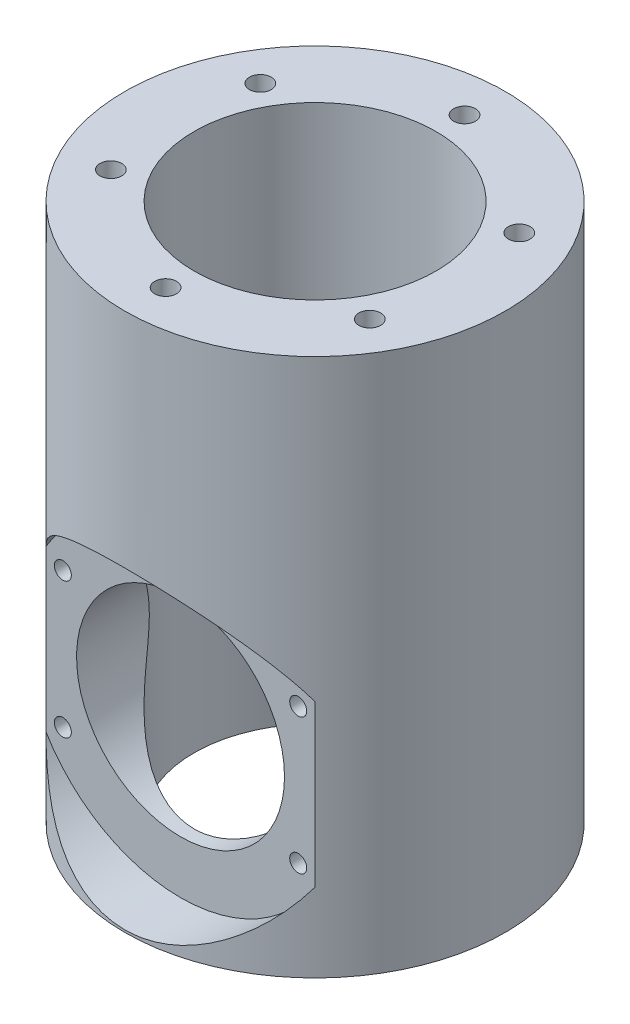
SolidWorks part; units mm, degrees
material "1060 Alloy"
ref_plane "Front Plane" through (0, 0, 0) normal (0, 0, 1) x (1, 0, 0)
ref_plane "Top Plane" through (0, 0, 0) normal (0, 1, 0) x (1, 0, 0)
ref_plane "Right Plane" through (0, 0, 0) normal (1, 0, 0) x (0, 0, -1)
sketch "Sketch1" plane through (0, 0, 0) normal (0, 0, 1) x (1, 0, 0)
  circle A0 centre (0, 0) radius 6.65
  circle A1 centre (0, 0) radius 7.15
  dimension "D1" = 13.3
  dimension "D2" = 14.3
extrude "Boss-Extrude1" add sketch "Sketch1" along normal blind 5
sketch "Sketch2" plane through (0, 0, 0) normal (0, 1, 0) x (1, 0, 0)
  circle A0 centre (0, 8.9) radius 8.9
  circle A1 centre (0, 8.9) radius 14
  dimension "D1" = 17.8
  dimension "D2" = 28
extrude "Boss-Extrude2" add sketch "Sketch2" along normal blind 27.9 and the other way blind 11.7
ref_plane "Plane4" through (0, -11.7, 0) normal (0, -1, 0) x (-1, 0, 0)
sketch "Sketch16" plane through (0, 0, 5) normal (0, 0, 1) x (1, 0, 0)
  circle A0 centre (0, 0) radius 6.65
  circle A1 centre (0, 0) radius 6.65 construction
  dimension "D1" = 0
extrude "Cut-Extrude3" cut sketch "Sketch16" against normal blind 17 and the other way blind 7
sketch "Sketch23" plane through (0, 0, 5) normal (0, 0, 1) x (1, 0, 0)
  circle A0 centre (0, 0) radius 7.05
  circle A1 centre (0, 0) radius 6.65
  circle A2 centre (0, 0) radius 6.65 construction
  dimension "D1" = 0
  dimension "D2" = 0.4
extrude "Cut-Extrude5" cut sketch "Sketch23" against normal blind 2
sketch "Sketch30" plane through (0, 0, 5) normal (0, 0, 1) x (1, 0, 0)
  circle A0 centre (0, 0) radius 7.65
  dimension "D1" = 15.3
extrude "Cut-Extrude8" cut sketch "Sketch30" against normal blind 11.28 and the other way blind 10
sketch "Sketch31" plane through (0, 27.9, 0) normal (0, 1, 0) x (1, 0, 0)
  circle A0 centre (0, 8.9) radius 11
  dimension "D1" = 22
hole_wizard "Tap Drill for M2 Tap1" positions "Sketch46" profile "Sketch47" hole size "M2" standard "ISO"
sketch "Sketch46" plane through (0, 27.9, 0) normal (0, 1, 0) x (1, 0, 0)
  circle A0 centre (0, 8.9) radius 8.9 construction
  point P0 (0, -2.1)
  dimension "D1" = 11
sketch "Sketch47" plane through (0, 27.9, 2.1) normal (1, 0, 0) x (0, 0, 1)
  line L0 (0, 0) -> (0, 4.4807)
  line L1 (0, 4.4807) -> (0.8, 4)
  line L2 (0.8, 4) -> (0.8, 0)
  line L5 (0.8, 0) -> (0, 0)
  line L10 (0, 4.4807) -> (-0.8, 4) construction
  line L11 (0, -6.35) -> (0, 107.95) construction
  dimension "Hole Dia." = 1.6
  dimension "Hole Depth" = 4
  dimension "Drill Angle" = 118
pattern_circular "CirPattern3" count 6 over 360 about axis through (0, -11.7, -8.9) along (0, 1, 0) of "Tap Drill for M2 Tap1" reverse direction yes
ref_plane "Plane6" through (0, 8.1, 0) normal (0, 1, 0) x (1, 0, 0)
mirror "Mirror1" about plane through (0, 8.1, 0) normal (0, 1, 0) of "CirPattern3"
sketch "Sketch39" plane through (0, -11.7, 0) normal (0, -1, 0) x (1, 0, 0)
  circle A0 centre (0, 2.1) radius 1.8168
extrude "Boss-Extrude3" add sketch "Sketch39" against normal up to surface (4.05 mm away) up to face at (0.5788, -7.6281, 2.4575)
sketch "Sketch38" plane through (0, 0, 0) normal (0, 0, 1) x (1, 0, 0)
  circle A0 centre (0, 0) radius 11.53
  dimension "D1" = 23.06
extrude "Cut-Extrude11" cut sketch "Sketch38" along normal blind 10 from offset 1 contours A0 region at (0, 0, 0)
hole_wizard "Tap Drill for M1.6 Tap1" positions "Sketch48" profile "Sketch49" hole size "M1.6" standard "ISO"
sketch "Sketch48" plane through (0, 0, 1) normal (0, 0, 1) x (1, 0, 0)
  line L0 (-14.573, 0) -> (17.3722, 0) construction
  line L2 (-8.6603, 5) -> (0, 0) construction
  point P0 (-8.6603, 5)
  dimension "D1" = 10
  dimension "D2" = 30
sketch "Sketch49" plane through (-8.6603, 5, 1) normal (1, 0, 0) x (0, -1, 0)
  line L0 (0, 0) -> (0, 5.3755)
  line L1 (0, 5.3755) -> (0.625, 5)
  line L2 (0.625, 5) -> (0.625, 0)
  line L5 (0.625, 0) -> (0, 0)
  line L10 (0, 5.3755) -> (-0.625, 5) construction
  line L11 (0, -6.35) -> (0, 107.95) construction
  dimension "Hole Dia." = 1.25
  dimension "Hole Depth" = 5
  dimension "Drill Angle" = 118
pattern_circular "CirPattern4" count 6 over 360 about axis through (0, 0, 15) along (0, 0, -1) skipping 2, 5 of "Tap Drill for M1.6 Tap1" reverse direction yes
